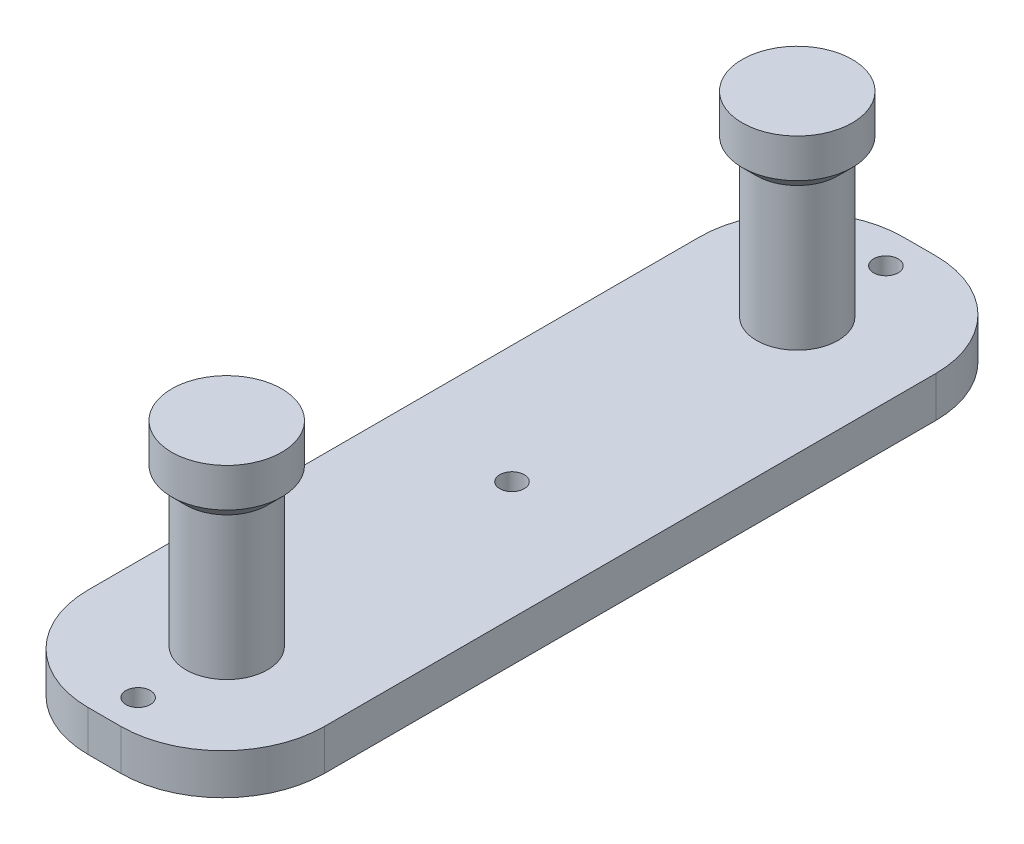
SolidWorks part; units mm, degrees
ref_plane "Front Plane" through (0, 0, 0) normal (0, 0, 1) x (1, 0, 0)
ref_plane "Top Plane" through (0, 0, 0) normal (0, 1, 0) x (1, 0, 0)
ref_plane "Right Plane" through (0, 0, 0) normal (1, 0, 0) x (0, 0, -1)
sketch "Sketch1" plane through (0, 0, 0) normal (0, 1, 0) x (1, 0, 0)
  line L0 (1.3004, 30.2354) -> (1.3004, -169.7646)
  line L1 (-27.6996, 30.2354) -> (30.3004, 30.2354)
  line L2 (-27.6996, 30.2354) -> (-27.6996, -169.7646)
  line L3 (-27.6996, -169.7646) -> (30.3004, -169.7646)
  line L4 (30.3004, 30.2354) -> (30.3004, -169.7646)
  circle A0 centre (1.3004, 0.2354) radius 10
  circle A1 centre (1.3004, -139.7646) radius 10
  dimension "D3" = 20
  dimension "D4" = 20
  dimension "D1" = 58
  dimension "D2" = 200
  dimension "D5" = 30
  dimension "D6" = 30
extrude "Boss-Extrude1" add sketch "Sketch1" along normal blind 10 contours A1 L0 L3 L4 L1 A0 | A1 L0 A0 L1 L2 L3 | L0 A0 | L0 A0 | L0 A1 | L0 A1 region at (16.3878, 0, 69.7646) region at (-13.7869, 0, 69.7646) region at (5.5446, 0, -0.2354) region at (-2.9437, 0, -0.2354) region at (5.5446, 0, 139.7646) region at (-2.9437, 0, 139.7646)
extrude "Boss-Extrude2" add sketch "Sketch1<3>" along normal blind 50 contours L0 A0 | L0 A0 | L0 A1 | L0 A1 region at (5.5446, 0, -0.2354) region at (-2.9437, 0, -0.2354) region at (5.5446, 0, 139.7646) region at (-2.9437, 0, 139.7646)
sketch "Sketch1<3>" plane through (0, 0, 0) normal (0, 1, 0) x (1, 0, 0) same geometry as "Sketch1"
sketch "Sketch3" plane through (0, 50, 0) normal (0, 1, 0) x (1, 0, 0)
  circle A0 centre (1.3004, -139.7646) radius 13.5
  circle A1 centre (1.3004, 0.2354) radius 13.5
  dimension "D1" = 27
  dimension "D2" = 27
extrude "Boss-Extrude3" add sketch "Sketch3" along normal blind 8 contours A1 | A0
chamfer "Chamfer2" distance 5 angle 45 2 edges at (1.3004, 50, 9.7646) (1.3004, 50, 149.7646)
fillet "Fillet1" radius 25 4 edges at (-27.6996, 5, -30.2354) (30.3004, 5, -30.2354) (-27.6996, 5, 169.7646) (30.3004, 5, 169.7646)
sketch "Sketch4" plane through (0, 10, 0) normal (0, 1, 0) x (1, 0, 0)
  line L0 (1.3004, 30.2354) -> (1.3004, 13.7354)
  line L1 (-2.6996, 30.2354) -> (5.3004, 30.2354) construction
  line L2 (1.3004, -13.2646) -> (1.3004, -126.2646)
  line L3 (1.3004, -153.2646) -> (1.3004, -169.7646)
  line L4 (-2.6996, -169.7646) -> (5.3004, -169.7646) construction
  circle A0 centre (1.3004, 0.2354) radius 13.5 construction
  circle A1 centre (1.3004, -139.7646) radius 13.5 construction
  circle A2 centre (1.3004, 21.9854) radius 3
  circle A3 centre (1.3004, -69.7646) radius 3
  circle A4 centre (1.3004, -161.5146) radius 3
  dimension "D1" = 6
  dimension "D2" = 6
  dimension "D3" = 6
extrude "Cut-Extrude1" cut sketch "Sketch4" against normal blind 10 contours L0 A2 | L0 A2 | L2 A3 | L2 A3 | L3 A4 | L3 A4 region at (2.5737, 10, -21.9854) region at (0.0272, 10, -21.9854) region at (2.5737, 10, 69.7646) region at (0.0272, 10, 69.7646) region at (2.5737, 10, 161.5146) region at (0.0272, 10, 161.5146)
